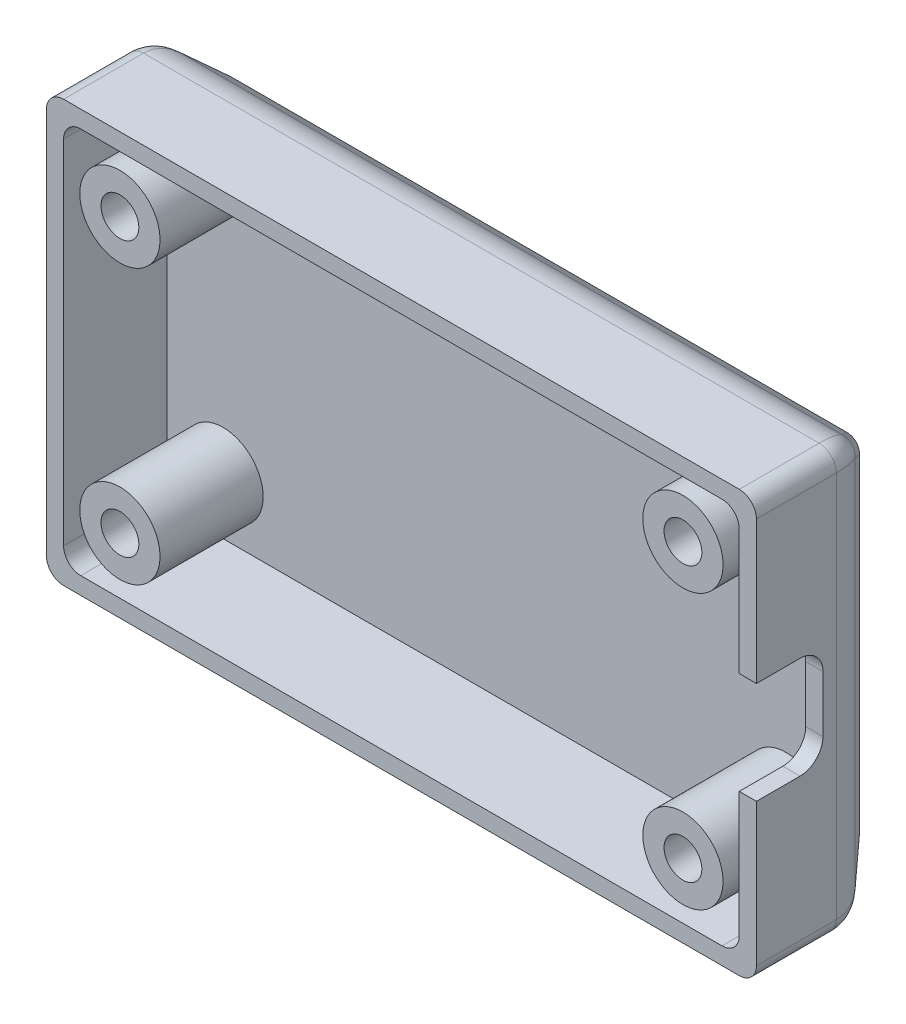
SolidWorks part; units mm, degrees
ref_plane "Alzado" through (0, 0, 0) normal (0, 0, 1) x (1, 0, 0)
ref_plane "Planta" through (0, 0, 0) normal (0, 1, 0) x (1, 0, 0)
ref_plane "Vista lateral" through (0, 0, 0) normal (1, 0, 0) x (0, 0, -1)
sketch "Croquis1" plane through (0, 0, 0) normal (0, 0, 1) x (1, 0, 0)
  line L1 (-21.6, 9) -> (21.6, 9) construction
  line L2 (-21.6, 9) -> (-21.6, -9) construction
  line L3 (-21.6, -9) -> (21.6, -9) construction
  line L4 (21.6, 9) -> (21.6, -9) construction
  line L5 (-21.6, 9) -> (21.6, -9) construction
  line L6 (-21.6, -9) -> (21.6, 9) construction
  line L7 (-22.6, 10) -> (22.6, 10) construction
  line L8 (-22.6, 10) -> (-22.6, -10) construction
  line L9 (-22.6, -10) -> (22.6, -10) construction
  line L10 (22.6, 10) -> (22.6, -10) construction
  line L11 (-22.6, 10) -> (22.6, -10) construction
  line L12 (-22.6, -10) -> (22.6, 10) construction
  line L18 (-27.974, 15.374) -> (-27.974, -15.374)
  line L20 (-27.974, -15.374) -> (27.974, -15.374)
  line L22 (27.974, -15.374) -> (27.974, 15.374)
  line L24 (27.974, 15.374) -> (-27.974, 15.374)
  line L25 (-30.975, -18.375) -> (30.975, -18.375)
  line L26 (-30.975, 18.375) -> (30.975, 18.375)
  line L27 (-30.975, 18.375) -> (-30.975, -18.375)
  line L29 (30.975, 18.375) -> (30.975, -18.375)
  line L30 (-30.975, 18.375) -> (30.975, -18.375) construction
  line L31 (-30.975, -18.375) -> (30.975, 18.375) construction
  circle A0 centre (-24.5622, 11.9622) radius 2.775
  circle A1 centre (-24.4031, -11.8031) radius 2.775
  circle A3 centre (24.5622, 11.9622) radius 2.775
  circle A4 centre (24.5622, -11.9622) radius 2.775
  point P0 (0, 0)
  point P6 (0, 0)
  point P19 (0, 0)
  dimension "D5" = 5.55
  dimension "D6" = 49.1244
  dimension "D1" = 43.2
  dimension "D2" = 18
  dimension "D3" = 45.2
  dimension "D4" = 20
  dimension "D7" = 61.95
  dimension "D8" = 36.75
  dimension "D9" = 23.7653
extrude "Saliente-Extruir1" add sketch "Croquis1" along normal blind 12 contours L27 L25 L29 L26 | A0 | A1 | A4 | A3
sketch "Croquis2" plane through (0, 0, 12) normal (0, 0, 1) x (1, 0, 0)
  line L0 (-46.0055, -20.2772) -> (-46.0055, -51.0253)
  line L1 (-46.0055, -51.0253) -> (9.9426, -51.0253)
  line L2 (9.9426, -51.0253) -> (9.9426, -20.2772)
  line L3 (9.9426, -20.2772) -> (-46.0055, -20.2772)
  line L5 (-29.475, 16.875) -> (29.475, 16.875)
  line L6 (-29.475, 16.875) -> (-29.475, -16.875)
  line L7 (-29.475, -16.875) -> (29.475, -16.875)
  line L8 (29.475, 16.875) -> (29.475, -16.875)
  line L9 (-29.475, 16.875) -> (29.475, -16.875) construction
  line L10 (-29.475, -16.875) -> (29.475, 16.875) construction
  point P4 (0, 0)
  dimension "D1" = 55.948
  dimension "D2" = 30.748
  dimension "D3" = 58.95
  dimension "D4" = 33.75
extrude "Cortar-Extruir1" cut sketch "Croquis2" against normal blind 9
chamfer "Chaflán4" distance 3 angle 50 4 edges at (-30.975, 0, 0) (0, -18.375, 0) (30.975, 0, 0) (0, 18.375, 0) first distance on face at (27.3372, -11.9622, 0)
fillet "Redondeo6" radius 4 4 edges at (0, 18.375, 3.5753) (-30.975, 0, 3.5753) (0, -18.375, 3.5753) (30.975, 0, 3.5753)
fillet "Redondeo7" radius 1.5 16 edges at (-30.975, -18.375, 8.5156) (-30.7338, -18.1338, 3.6631) (-29.0071, -16.4071, 1.23) (29.0071, 16.4071, 1.23) (30.7338, 18.1338, 3.6631) (29.0071, -16.4071, 1.23) (30.7338, -18.1338, 3.6631) (-29.0071, 16.4071, 1.23) (-30.7338, 18.1338, 3.6631) (30.975, 18.375, 8.5156) (30.975, -18.375, 8.5156) (-30.975, 18.375, 8.5156) (29.475, -16.875, 7.5) (29.475, 16.875, 7.5) (-29.475, 16.875, 7.5) (-29.475, -16.875, 7.5)
sketch "Croquis3" plane through (0, 0, 3) normal (0, 0, 1) x (1, 0, 0)
  line L1 (-29.826, 17.2183) -> (29.826, 17.2183)
  line L2 (-29.826, 17.2183) -> (-29.826, -17.2183)
  line L3 (-29.826, -17.2183) -> (29.826, -17.2183)
  line L4 (29.826, 17.2183) -> (29.826, -17.2183)
  line L5 (-29.826, 17.2183) -> (29.826, -17.2183) construction
  line L6 (-29.826, -17.2183) -> (29.826, 17.2183) construction
  point P0 (0, 0)
sketch "Croquis4" plane through (0, 0, 3) normal (0, 0, 1) x (1, 0, 0)
  circle A0 centre (-24.5622, 11.9622) radius 3.5
  circle A1 centre (-24.5622, 11.9622) radius 1.65
extrude "Saliente-Extruir2" add sketch "Croquis4" along normal up to surface (9 mm away) up to face at (0, 0, 12)
mirror "Simetría1" about plane through (0, 0, 0) normal (1, 0, 0) of "Saliente-Extruir2" second plane through (0, 0, 0) second plane normal (0, 1, 0)
sketch "Croquis5" plane through (30.975, 0, 0) normal (1, 0, 0) x (0, 0, -1)
  line L4 (-12, 16.875) -> (-12, -16.875) construction
  line L8 (-12, 4.45) -> (-12, -4.45)
  line L9 (-6.2, 4.45) -> (-6.2, -4.45)
  line L11 (-12, 4.45) -> (-6.2, 4.45)
  line L13 (-6.2, -4.45) -> (-12, -4.45)
  dimension "D3" = 8.9
extrude "Cortar-Extruir2" cut sketch "Croquis5" against normal blind 8
fillet "Redondeo8" radius 2 2 edges at (30.225, -4.45, 6.2) (30.225, 4.45, 6.2)
